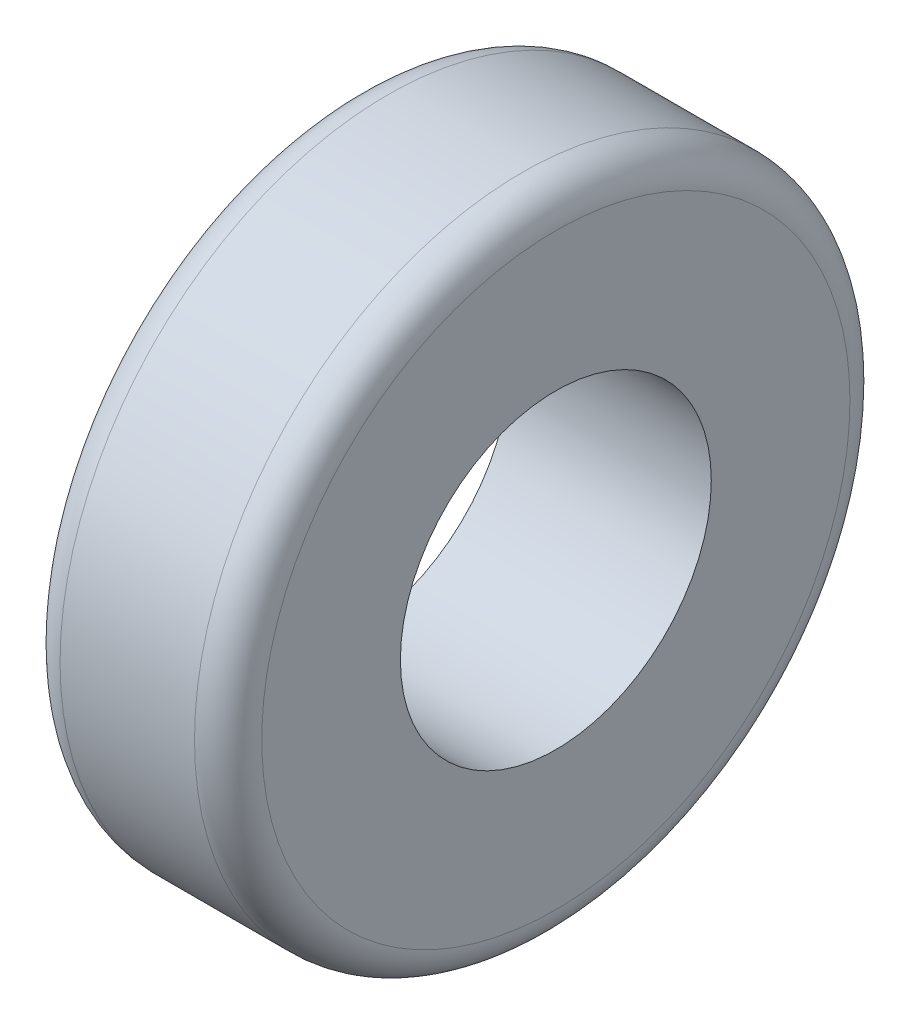
SolidWorks part; units mm, degrees
ref_plane "Front" through (0, 0, 0) normal (0, 0, 1) x (1, 0, 0)
ref_plane "Top" through (0, 0, 0) normal (0, 1, 0) x (1, 0, 0)
ref_plane "Right" through (0, 0, 0) normal (1, 0, 0) x (0, 0, -1)
sketch "Sketch1" plane through (0, 0, 0) normal (1, 0, 0) x (0, 0, -1)
  circle A0 centre (-57.867, 49.7716) radius 123.825
  circle A1 centre (-57.867, 49.7716) radius 58.7375
  dimension "D1" = 247.65
  dimension "D2" = 117.475
extrude "Boss-Extrude1" add sketch "Sketch1" along normal blind 76.2
fillet "Fillet1" radius 12.7 2 edges at (0, 49.7716, -65.958) (76.2, 49.7716, -65.958)
